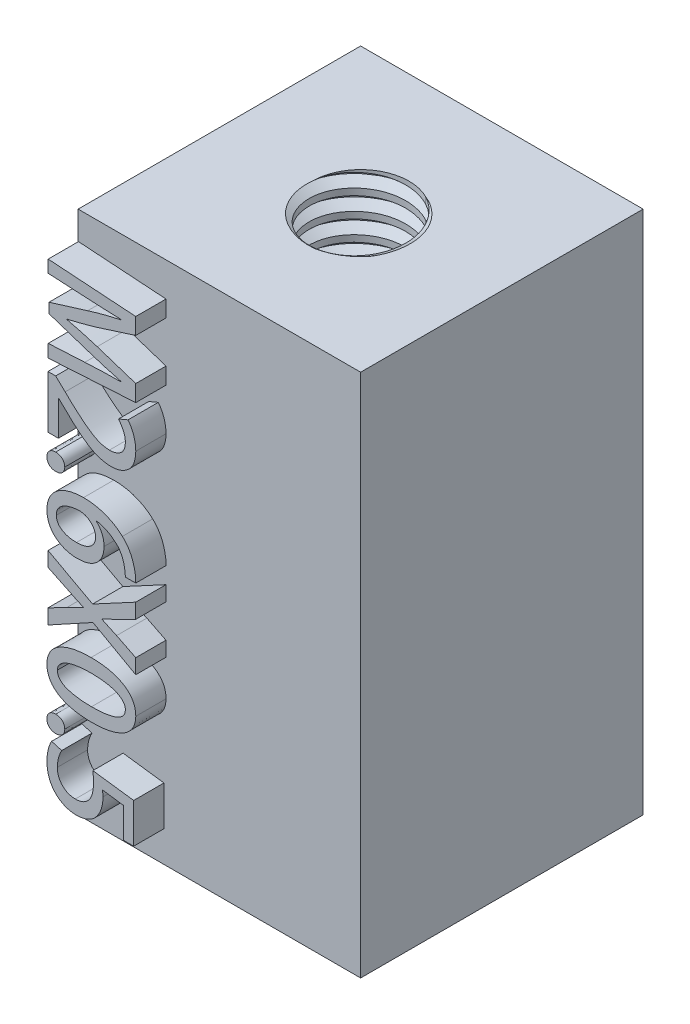
SolidWorks part; units mm, degrees
ref_plane "Alzado" through (0, 0, 0) normal (0, 0, 1) x (1, 0, 0)
ref_plane "Planta" through (0, 0, 0) normal (0, 1, 0) x (1, 0, 0)
ref_plane "Vista lateral" through (0, 0, 0) normal (1, 0, 0) x (0, 0, -1)
sketch "Croquis1" plane through (0, 0, 0) normal (0, 1, 0) x (1, 0, 0)
  line L1 (-3.5, 3.5) -> (3.5, 3.5)
  line L2 (-3.5, 3.5) -> (-3.5, -3.5)
  line L3 (-3.5, -3.5) -> (3.5, -3.5)
  line L4 (3.5, 3.5) -> (3.5, -3.5)
  line L5 (-3.5, 3.5) -> (3.5, -3.5) construction
  line L6 (-3.5, -3.5) -> (3.5, 3.5) construction
  circle A0 centre (0, 0) radius 1.2
  point P0 (0, 0)
  dimension "D1" = 2.4
  dimension "7" = 7
extrude "Saliente-Extruir1" add sketch "Croquis1" along normal blind 13
sketch "Croquis2" plane through (0, 0, 3.5) normal (0, 0, 1) x (1, 0, 0)
  text T0 "M2.6X0.5" font "@Adobe Heiti Std R" height in points 7
split line "Línea de partición1"
extrude "Saliente-Extruir2" add sketch "Croquis2<2>" along normal blind 0.75
sketch "Croquis2<2>" plane through (0, 0, 3.5) normal (0, 0, 1) x (1, 0, 0) same geometry as "Croquis2"
thread "Rosca1" pitch 0.45 method cut profile "Perfil de rosca1" start angle 0, offset 1, length 11, pitch 0.5, diameter 2.4
ref_plane "Plano1" through (-1.2, 14, 0) normal (0, 0, 1) x (-1, 0, 0)
sketch "Perfil de rosca1" plane through (-1.2, 14, 0) normal (0, 0, 1) x (-1, 0, 0)
  line L0 (0, 0) -> (0, 0.45) construction
  line L1 (0, 0) -> (0.2436, 0.1406)
  line L2 (0.2436, 0.1406) -> (0.2436, 0.1969)
  line L3 (0.2436, 0.1969) -> (0, 0.3375)
  line L4 (0.2436, 0.1687) -> (0, 0.1687) construction
  line L11 (0, 0) -> (0, 0.3375)
  point P2 (0, 0)
  dimension "Pitch" = 0.45
  dimension "Profile_Angle" = 60
  dimension "Profile_Land" = 0.0562
  dimension "Profile_Height" = 0.2436
